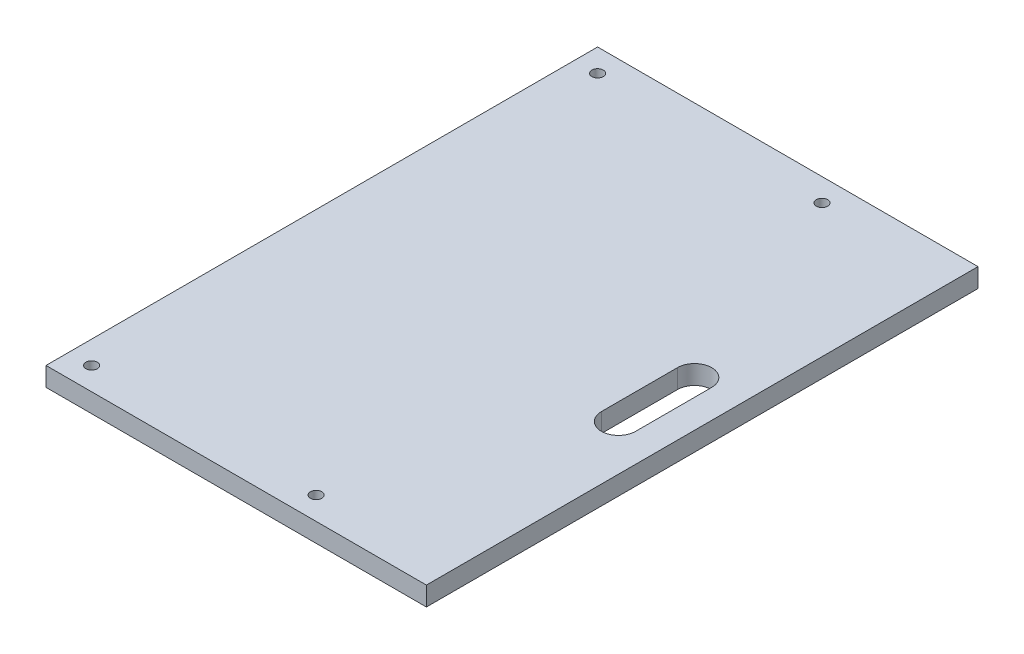
SolidWorks part; units mm, degrees
ref_plane "Front Plane" through (0, 0, 0) normal (0, 0, 1) x (1, 0, 0)
ref_plane "Top Plane" through (0, 0, 0) normal (0, 1, 0) x (1, 0, 0)
ref_plane "Right Plane" through (0, 0, 0) normal (1, 0, 0) x (0, 0, -1)
sketch "Sketch1" plane through (0, 0, 0) normal (0, 1, 0) x (1, 0, 0)
  line L0 (83.5, 82.5) -> (83.5, 62.5)
  line L1 (0, 0) -> (100, 0)
  line L2 (0, 0) -> (0, 145)
  line L3 (0, 145) -> (100, 145)
  line L4 (100, 0) -> (100, 145)
  line L5 (92.5, 82.5) -> (92.5, 62.5)
  line L6 (83.5, 72.5) -> (92.5, 72.5) construction
  arc A0 (92.5, 82.5) -> (83.5, 82.5) centre (88, 82.5) ccw
  arc A1 (92.5, 62.5) -> (83.5, 62.5) centre (88, 62.5) cw
  point P7 (0, 72.5)
  dimension "D3" = 4.5
  dimension "D1" = 145
  dimension "D2" = 100
  dimension "D4" = 10
  dimension "D5" = 12
extrude "Boss-Extrude1" add sketch "Sketch1" along normal blind 5
sketch "Sketch2" plane through (0, 5, 0) normal (0, 1, 0) x (1, 0, 0)
  line L0 (0, 145) -> (0, 0) construction
  line L1 (0, 0) -> (100, 0) construction
  line L2 (100, 145) -> (0, 145) construction
  circle A0 centre (6, 139) radius 1.5
  circle A1 centre (6, 6) radius 1.5
  circle A2 centre (65, 139) radius 1.5
  circle A3 centre (65, 6) radius 1.5
  dimension "D1" = 3
  dimension "D2" = 6
  dimension "D3" = 6
  dimension "D4" = 6
  dimension "D5" = 59
extrude "Cut-Extrude1" cut sketch "Sketch2" against normal through all
